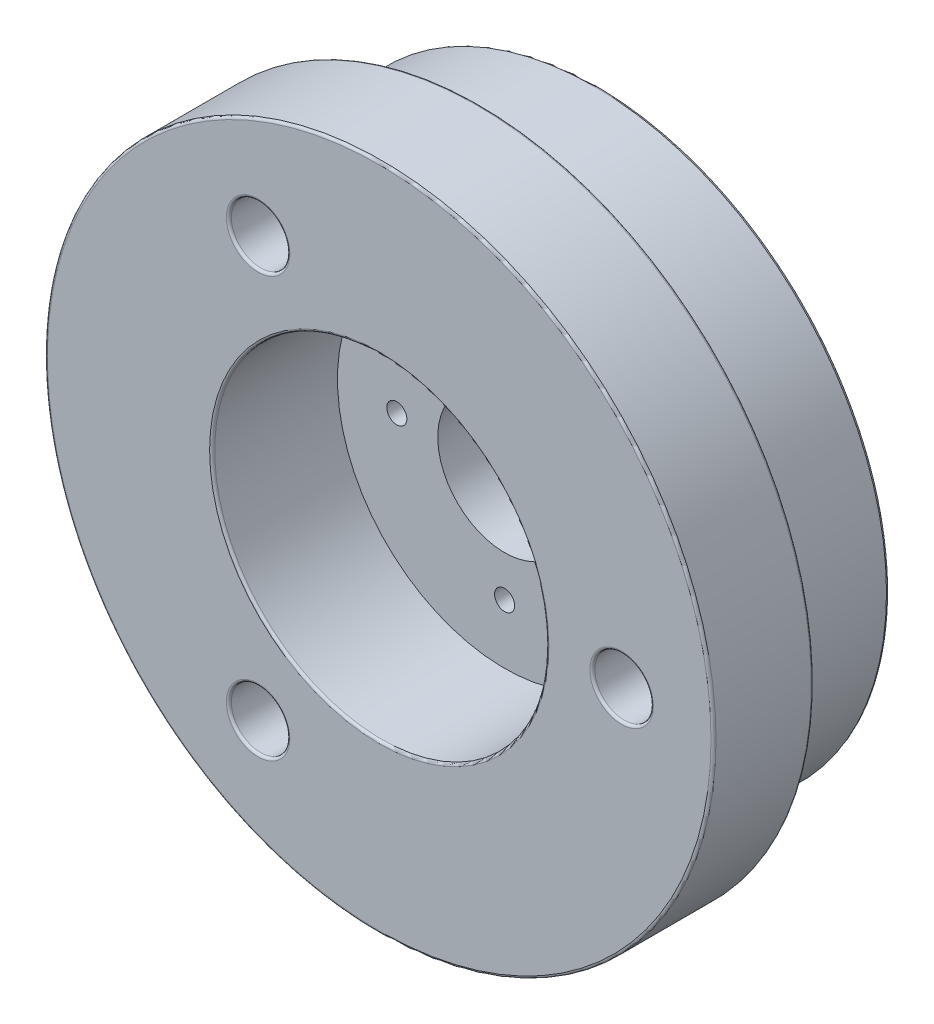
SolidWorks part; units mm, degrees
ref_plane "Płaszczyzna przednia" through (0, 0, 0) normal (0, 0, 1) x (1, 0, 0)
ref_plane "Płaszczyzna górna" through (0, 0, 0) normal (0, 1, 0) x (1, 0, 0)
ref_plane "Płaszczyzna prawa" through (0, 0, 0) normal (1, 0, 0) x (0, 0, -1)
sketch "Szkic1" plane through (0, 0, 0) normal (0, 1, 0) x (1, 0, 0)
  line L0 (0, 0) -> (-20, 0)
  line L1 (-20, 0) -> (-20, 6)
  line L2 (-20, 6) -> (-17.5, 6)
  line L3 (-17.5, 6) -> (-17.5, 13)
  line L4 (-17.5, 13) -> (0, 13)
  line L5 (0, 13) -> (0, 0)
  dimension "D1" = 6
  dimension "D2" = 20
  dimension "D3" = 13
  dimension "D4" = 17.5
revolve "Obrót1" add sketch "Szkic1" angle 360 about L5
sketch "Szkic2" plane through (0, 0, 0) normal (0, 0, 1) x (1, 0, 0)
  circle A0 centre (0, 0) radius 10
  circle A1 centre (14.5, 0) radius 1.75
  circle A2 centre (-7.25, -12.5574) radius 1.75
  circle A3 centre (-7.25, 12.5574) radius 1.75
  circle A4 centre (0, 0) radius 20 construction
  circle A5 centre (0, 0) radius 4
  circle A6 centre (6.45, 0) radius 0.6
  circle A7 centre (0, -6.45) radius 0.6
  circle A8 centre (-6.45, 0) radius 0.6
  circle A9 centre (0, 6.45) radius 0.6
  point P12 (0, 0)
  point P24 (0, 0)
  dimension "D1" = 20
  dimension "D2" = 3.5
  dimension "D5" = 14.5
  dimension "D6" = 14.5
  dimension "D7" = 8
  dimension "D8" = 1.2
  dimension "D3" = 14.5
  dimension "D9" = 6.45
  dimension "D11" = 6.45
  dimension "D4" = 3
  dimension "D10" = 4
extrude "Wytnij-wyciągnięcie1" cut sketch "Szkic2" against normal through all contours A8 | A5 | A7 | A6 | A9 | A3 | A2 | A1
extrude "Wytnij-wyciągnięcie3" cut sketch "Szkic2<4>" against normal blind 7.5
sketch "Szkic2<4>" plane through (0, 0, 0) normal (0, 0, 1) x (1, 0, 0) same geometry as "Szkic2"
fillet "Zaokrąglenie1" radius 0.15 16 edges at (-17.5, 0, -6) (-20, 0, -6) (-17.5, 0, -13) (-5.85, 0, -13) (16.25, 0, -13) (-5.5, -12.5574, -13) (-5.5, 12.5574, -13) (4, 0, -13) (0.6, -6.45, -13) (7.05, 0, -13) (0.6, 6.45, -13) (-20, 0, 0) (16.25, 0, 0) (-5.5, -12.5574, 0) (-5.5, 12.5574, 0) (10, 0, 0)
